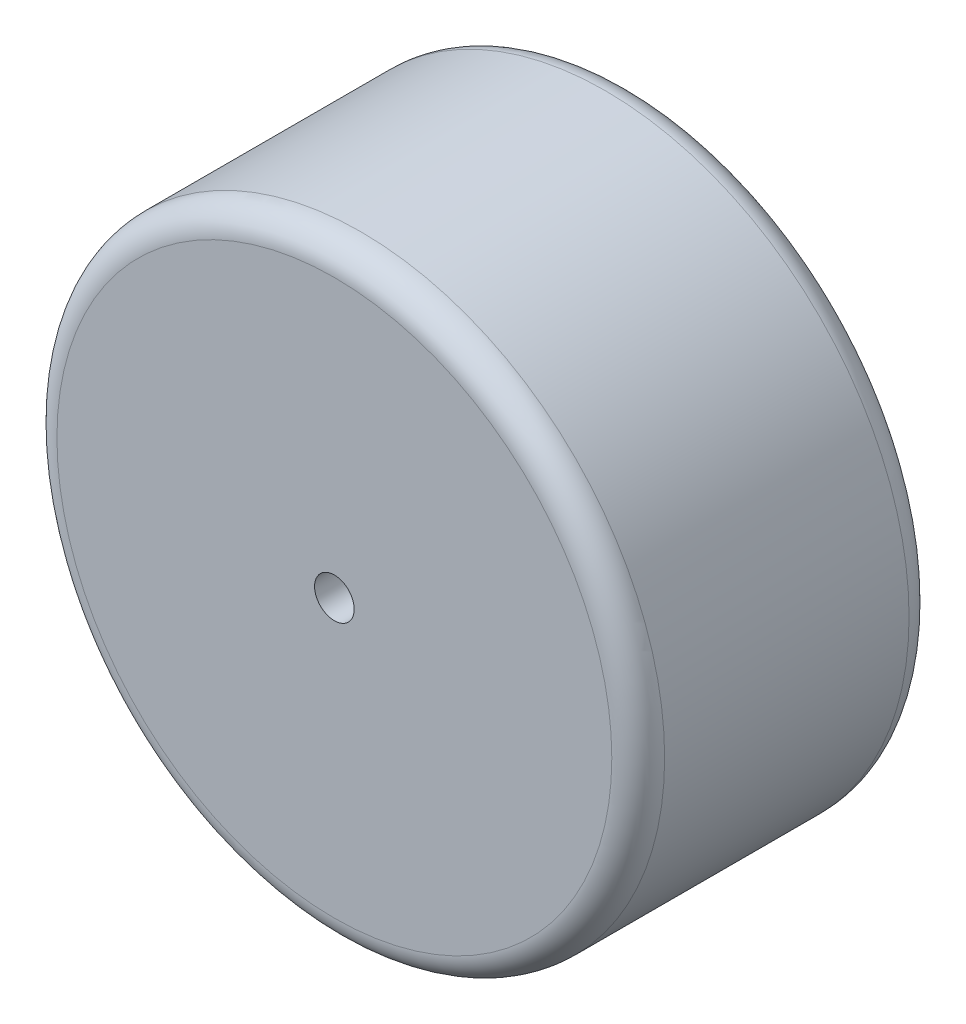
SolidWorks part; units mm, degrees
ref_plane "Front Plane" through (0, 0, 0) normal (0, 0, 1) x (1, 0, 0)
ref_plane "Top Plane" through (0, 0, 0) normal (0, 1, 0) x (1, 0, 0)
ref_plane "Right Plane" through (0, 0, 0) normal (1, 0, 0) x (0, 0, -1)
ref_plane "Plane1" through (0, 0, 10) normal (0, 0, 1) x (1, 0, 0)
sketch "Sketch1" plane through (0, -10, 10) normal (0, 0, -1) x (1, 0, 0)
  circle A0 centre (-29.7253, 4.3466) radius 23
  dimension "D1" = 46
extrude "Boss-Extrude1" add sketch "Sketch1" along normal blind 22.5 contours A0
sketch "Sketch3" plane through (0, 0, 10) normal (0, 0, 1) x (1, 0, 0)
  circle A0 centre (-29.7253, -14.3466) radius 1.5
  dimension "D1" = 3
extrude "Cut-Extrude1" cut sketch "Sketch3" against normal through all
fillet "Fillet1" radius 2 2 edges at (-52.7253, -14.3466, -12.5) (-52.7253, -14.3466, 10)
